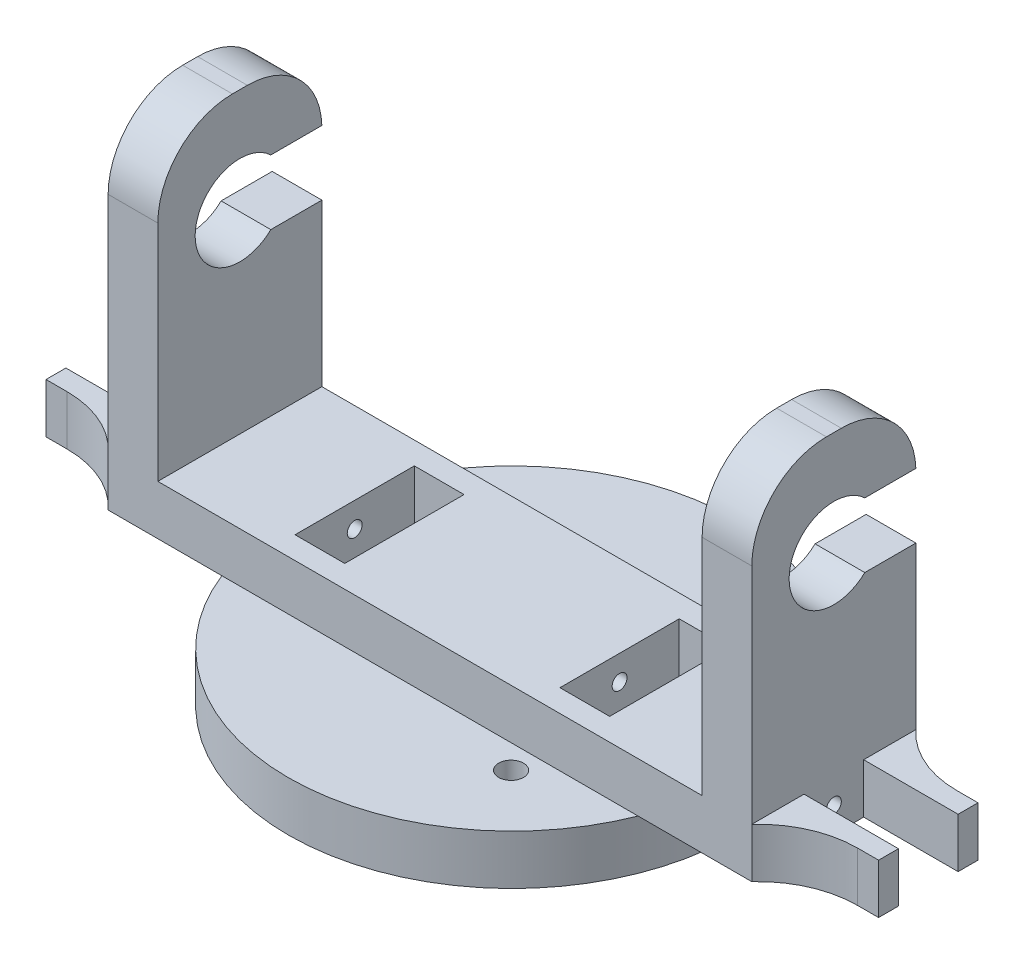
SolidWorks part; units mm, degrees
ref_plane "Front Plane" through (0, 0, 0) normal (0, 0, 1) x (1, 0, 0)
ref_plane "Top Plane" through (0, 0, 0) normal (0, 1, 0) x (1, 0, 0)
ref_plane "Right Plane" through (0, 0, 0) normal (1, 0, 0) x (0, 0, -1)
sketch "Sketch1" plane through (0, 0, 0) normal (0, 1, 0) x (1, 0, 0)
  line L1 (-64.745, 16.5) -> (64.745, 16.5)
  line L2 (-64.745, 16.5) -> (-64.745, -16.5)
  line L3 (-64.745, -16.5) -> (64.745, -16.5)
  line L4 (64.745, 16.5) -> (64.745, -16.5)
  point P4 (-64.745, 0)
  point P6 (0, 16.5)
  dimension "D1" = 33
  dimension "D2" = 129.49
extrude "Boss-Extrude1" add sketch "Sketch1" along normal blind 10 contours L1 L4 L3 L2
sketch "Sketch2" plane through (0, 10, 0) normal (0, 1, 0) x (1, 0, 0)
  line L0 (-64.745, -16.5) -> (64.745, -16.5) construction
  line L1 (-64.745, 16.5) -> (-54.745, 16.5)
  line L2 (-64.745, 16.5) -> (-64.745, -16.5)
  line L3 (-64.745, -16.5) -> (-54.745, -16.5)
  line L4 (-54.745, 16.5) -> (-54.745, -16.5)
  line L11 (0, 0) -> (0, 32.5393) construction
  line L12 (54.745, 16.5) -> (54.745, -16.5)
  line L13 (64.745, -16.5) -> (54.745, -16.5)
  line L14 (64.745, 16.5) -> (64.745, -16.5)
  line L15 (64.745, 16.5) -> (54.745, 16.5)
  dimension "D1" = 54.745
extrude "Boss-Extrude2" add sketch "Sketch2" along normal blind 60
sketch "Sketch3" plane through (64.745, 0, 0) normal (1, 0, 0) x (0, 0, -1)
  line L1 (16.5, 55.5) -> (6.2249, 55.5)
  line L2 (16.5, 70) -> (16.5, 0) construction
  line L3 (16.5, 42.5) -> (6.2249, 42.5)
  line L4 (16.5, 55.5) -> (16.5, 42.5)
  line L6 (16.5, 0) -> (-16.5, 0) construction
  arc A0 (6.2249, 55.5) -> (6.2249, 42.5) centre (0, 49) ccw
  point P11 (16.5, 49)
  dimension "D1" = 18
  dimension "D2" = 49
  dimension "D3" = 13
extrude "Cut-Extrude1" cut sketch "Sketch3" against normal through all
sketch "Sketch10" plane through (0, 0, 0) normal (0, -1, 0) x (1, 0, 0)
  circle A0 centre (0, 0) radius 45
  dimension "90" = 90
extrude "Boss-Extrude5" add sketch "Sketch10" along normal blind 10
sketch "Sketch9" plane through (0, 10, 0) normal (0, 1, 0) x (1, 0, 0)
  line L1 (-31.645, 12) -> (-21.645, 12)
  line L2 (-31.645, 12) -> (-31.645, -12)
  line L3 (-31.645, -12) -> (-21.645, -12)
  line L4 (-21.645, 12) -> (-21.645, -12)
  line L5 (-54.745, -16.5) -> (-54.745, 16.5) construction
  line L6 (0, 0) -> (0, 22.2113) construction
  line L7 (21.645, 12) -> (21.645, -12)
  line L8 (31.645, -12) -> (21.645, -12)
  line L9 (31.645, 12) -> (31.645, -12)
  line L10 (31.645, 12) -> (21.645, 12)
  line L11 (54.745, 16.5) -> (54.745, -16.5) construction
  circle A0 centre (0, 0) radius 30 construction
  circle A1 centre (21.1187, -21.3073) radius 2.5
  circle A4 centre (21.3073, 21.1187) radius 2.5
  circle A5 centre (-21.1187, 21.3073) radius 2.5
  point P4 (-44.9741, 12)
  point P8 (-21.645, 0)
  point P20 (-54.745, 12)
  dimension "D3" = 60
  dimension "D4" = 5
  dimension "D5" = 5
  dimension "D7" = 5
  dimension "D1" = 24
  dimension "D2" = 10
  dimension "D6" = 90
  dimension "D8" = 90
  dimension "D9" = 23.1
  dimension "D10" = 23.1
extrude "Cut-Extrude3" cut sketch "Sketch9" against normal through all
sketch "Sketch13" plane through (-64.745, 0, 0) normal (-1, 0, 0) x (0, 0, 1)
  line L1 (23.8073, 0) -> (18.8073, 0) construction
  circle A0 centre (0, 5) radius 1.5
  dimension "D2" = 3
  dimension "D1" = 5
fillet "Fillet1" radius 15 4 edges at (-59.745, 70, -16.5) (-59.745, 70, 16.5) (59.745, 70, 16.5) (59.745, 70, -16.5)
sketch "Sketch16" plane through (64.745, 0, 0) normal (1, 0, 0) x (0, 0, -1)
  line L0 (-6, 0) -> (-6, 10)
  line L1 (16.5, 0) -> (-16.5, 0) construction
  line L2 (-6, 10) -> (-10, 10)
  line L3 (-16.5, 0) -> (16.5, 0) construction
  line L4 (-10, 10) -> (-10, 0)
  line L6 (10, 0) -> (10, 10)
  line L7 (10, 10) -> (6, 10)
  line L8 (6, 10) -> (6, 0)
  line L11 (-10, 0) -> (-6, 0)
  line L12 (6, 0) -> (10, 0)
  line L13 (10, 0) -> (6, 0)
  line M12 (-16.5, 0) -> (16.5, 0)
  dimension "D1" = 6
  dimension "D2" = 6
  dimension "D3" = 10
  dimension "D5" = 20
  dimension "D6" = 4
extrude "Boss-Extrude13" add sketch "Sketch16" along normal blind 19 contours L7 L8 L6 M12 | L2 L4 L0 M12 region at (64.745, 5, 8) region at (64.745, 5, -8)
sketch "Sketch18" plane through (-64.745, 0, 0) normal (-1, 0, 0) x (0, 0, 1)
  line L1 (-10, 10) -> (-6, 10)
  line L2 (-10, 10) -> (-10, 0)
  line L4 (-6, 10) -> (-6, 0)
  line L5 (-16.5, 0) -> (16.5, 0) construction
  line L7 (10, 10) -> (6, 10)
  line L8 (10, 10) -> (10, 0)
  line L10 (6, 10) -> (6, 0)
  line L14 (-10, 0) -> (-6, 0)
  line L15 (6, 0) -> (10, 0)
  dimension "D1" = 4
  dimension "D2" = 10
  dimension "D3" = 6
  dimension "D4" = 6
  dimension "D5" = 10
  dimension "D6" = 4
extrude "Boss-Extrude19" add sketch "Sketch18" along normal blind 19
fillet "Fillet3" radius 20 4 edges at (-64.745, 5, -10) (-64.745, 5, 10) (64.745, 5, 10) (64.745, 5, -10)
extrude "Cut-Extrude4" cut sketch "Sketch13" against normal through all contours A0
